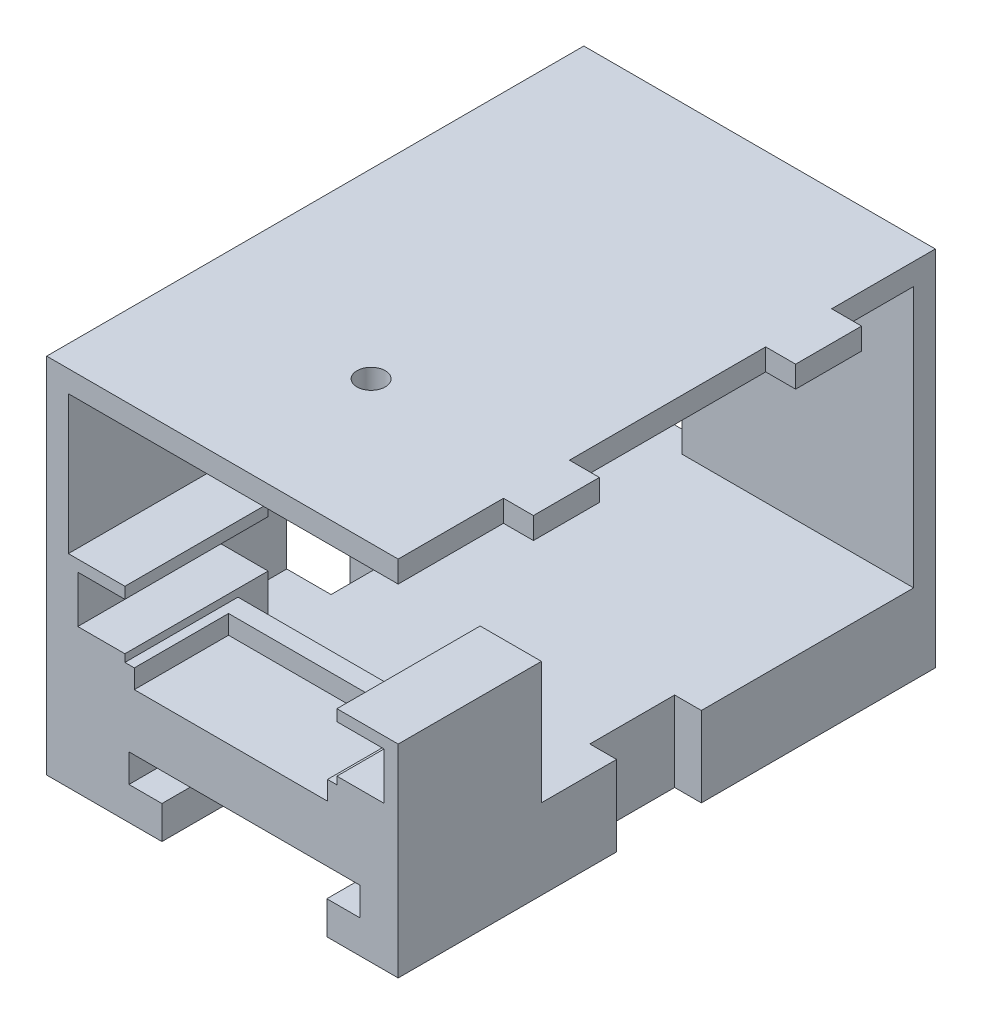
SolidWorks part; units mm, degrees
ref_plane "Front Plane" through (0, 0, 0) normal (0, 0, 1) x (1, 0, 0)
ref_plane "Top Plane" through (0, 0, 0) normal (0, 1, 0) x (1, 0, 0)
ref_plane "Right Plane" through (0, 0, 0) normal (1, 0, 0) x (0, 0, -1)
ref_plane "Plane3" through (0, 0, 53.83) normal (0, 0, 1) x (1, 0, 0)
sketch "Sketch1" plane through (0, 0, 0) normal (1, 0, 0) x (0, 0, -1)
  line L0 (0, 40.694) -> (0, 2.194)
  line L1 (0, 1.7462) -> (0, -1.7462) construction
  line L8 (-53.825, 2.194) -> (-53.825, 40.694)
  line L13 (-53.825, 40.694) -> (0, 40.694)
  line L19 (-53.825, 2.194) -> (0, 2.194)
  dimension "D1" = 0
extrude "main extrude" add sketch "Sketch1" along normal blind 2.3
sketch "Sketch3" plane through (2.3, 0, 0) normal (1, 0, 0) x (0, 0, -1)
  line L4 (-2.3, 38.394) -> (-2.3, 10.694)
  line L8 (-53.825, 38.394) -> (-2.3, 38.394)
  line L13 (-53.825, 40.694) -> (-53.825, 38.394)
  line L14 (-53.825, 40.694) -> (0, 40.694)
  line L15 (0, 40.694) -> (0, 2.194)
  line L16 (0, 2.194) -> (-53.825, 2.194)
  line L19 (-53.825, 10.694) -> (-2.3, 10.694)
  line L20 (-53.825, 40.694) -> (-53.825, 2.194) construction
  line L22 (-53.825, 10.694) -> (-53.825, 2.194)
  dimension "D1" = 2.3
  dimension "D2" = 2.3
extrude "walls" add sketch "Sketch3" along normal blind 35
sketch "Sketch36" plane through (0, 0, 53.825) normal (0, 0, 1) x (1, 0, 0)
  line L0 (37.3, 40.694) -> (0, 40.694) construction
  line L1 (8, 40.694) -> (15, 40.694)
  line L2 (8, 40.694) -> (8, 38.394)
  line L3 (8, 38.394) -> (15, 38.394)
  line L4 (15, 40.694) -> (15, 38.394)
  line L5 (37.3, 38.394) -> (2.3, 38.394) construction
  line L6 (37.3, 38.394) -> (2.3, 38.394) construction
  line L7 (23, 40.694) -> (30, 40.694)
  line L8 (23, 40.694) -> (23, 38.394)
  line L9 (23, 38.394) -> (30, 38.394)
  line L10 (30, 40.694) -> (30, 38.394)
  line L11 (0, 40.694) -> (0, 2.194) construction
  line L12 (0, 32.694) -> (2.3, 32.694)
  line L13 (0, 32.694) -> (0, 25.694)
  line L14 (0, 25.694) -> (2.3, 25.694)
  line L15 (2.3, 32.694) -> (2.3, 25.694)
  line L16 (2.3, 38.394) -> (2.3, 10.694) construction
  line L17 (2.3, 38.394) -> (2.3, 10.694) construction
  line L18 (0, 17.694) -> (2.3, 17.694)
  line L19 (0, 17.694) -> (0, 10.694)
  line L20 (0, 10.694) -> (2.3, 10.694)
  line L21 (2.3, 17.694) -> (2.3, 10.694)
  dimension "D1" = 8
  dimension "D2" = 8
  dimension "D3" = 7
  dimension "D4" = 7
  dimension "D5" = 7
  dimension "D6" = 7
  dimension "D7" = 8
  dimension "D8" = 8
extrude "Puzzle (main walls)" add sketch "Sketch36" along normal blind 3.175
sketch "Sketch25" plane through (0, 0, 2.3) normal (0, 0, 1) x (1, 0, 0)
  line L1 (2.3, 10.694) -> (12.703, 10.694)
  line L2 (2.3, 10.694) -> (2.3, 17.2991)
  line L3 (2.3, 17.2991) -> (12.703, 17.2991)
  line L4 (12.703, 10.694) -> (12.703, 17.2991)
extrude "Wire Hole" cut sketch "Sketch25" against normal through all
sketch "Sketch19" plane through (0, 10.694, 0) normal (0, 1, 0) x (1, 0, 0)
  line L16 (37.3, -41.8) -> (37.3, -53.825)
  line L18 (30.8, -53.825) -> (37.3, -53.825)
  line L27 (37.3, 0) -> (37.3, -53.825) construction
  line L40 (30.8, -53.825) -> (30.8, -41.8)
  line L41 (30.8, -41.8) -> (37.3, -41.8)
  line L47 (2.3, -53.825) -> (8.3, -53.825)
  line L48 (2.3, -53.825) -> (2.3, -41.8)
  line L49 (2.3, -41.8) -> (8.3, -41.8)
  line L50 (8.3, -53.825) -> (8.3, -41.8)
extrude "IR mount" add sketch "Sketch19" along normal blind 7
sketch "Sketch24" plane through (0, 0, 53.83) normal (0, 0, 1) x (1, 0, 0)
  line L0 (37.3, 2.194) -> (0, 2.194) construction
  line L1 (12.23, 2.194) -> (29.73, 2.194)
  line L2 (12.23, 2.194) -> (12.23, 5.694)
  line L4 (29.73, 2.194) -> (29.73, 5.694)
  line L5 (12.23, 5.694) -> (8.73, 5.694)
  line L6 (8.73, 5.694) -> (8.73, 8.694)
  line L9 (33.23, 8.694) -> (33.23, 5.694)
  line L10 (33.23, 5.694) -> (29.73, 5.694)
  line L11 (0, 10.694) -> (0, 2.194) construction
  line L12 (8.73, 8.694) -> (33.23, 8.694)
  dimension "D1" = 8.73
  dimension "D2" = 0
  dimension "D3" = 3.5
  dimension "D4" = 3
  dimension "D5" = 3
  dimension "D6" = 3.5
  dimension "D7" = 3.5
  dimension "D8" = 3.5
  dimension "D9" = 17.5
extrude "Magnet Mount Hole" cut sketch "Sketch24" against normal blind 51.83
sketch "Sketch40" plane through (0, 40.694, 0) normal (0, 1, 0) x (1, 0, 0)
  line L0 (37.3, 0) -> (37.3, -53.825) construction
  line L1 (0, 0) -> (0, -53.825) construction
  circle A0 centre (19.3, -41.8726) radius 1.5
  dimension "D1" = 3
  dimension "D2" = 18
  dimension "D3" = 19.3
extrude "LED Space" cut sketch "Sketch40" against normal blind 3
sketch "Sketch42" plane through (37.3, 0, 0) normal (1, 0, 0) x (0, 0, -1)
  line L0 (0, 40.694) -> (-53.825, 40.694) construction
  line L1 (-45.825, 40.694) -> (-38.825, 40.694)
  line L2 (-45.825, 40.694) -> (-45.825, 38.394)
  line L3 (-45.825, 38.394) -> (-38.825, 38.394)
  line L4 (-38.825, 40.694) -> (-38.825, 38.394)
  line L5 (-53.825, 38.394) -> (-2.3, 38.394) construction
  line L6 (-53.825, 38.394) -> (-2.3, 38.394) construction
  line L7 (-18, 40.694) -> (-11, 40.694)
  line L8 (-18, 40.694) -> (-18, 38.394)
  line L9 (-18, 38.394) -> (-11, 38.394)
  line L10 (-11, 40.694) -> (-11, 38.394)
  line L11 (-53.825, 40.694) -> (-53.825, 38.394) construction
  line L12 (0, 2.194) -> (0, 40.694) construction
  dimension "D1" = 8
  dimension "D2" = 7
  dimension "D3" = 7
  dimension "D4" = 11
extrude "Boss-Extrude15" add sketch "Sketch42" along normal blind 3.175
sketch "Sketch44" plane through (0, 17.694, 0) normal (0, 1, 0) x (1, 0, 0)
  line L1 (2.3, -41.8) -> (8.3, -41.8)
  line L2 (2.3, -41.8) -> (2.3, -53.825)
  line L3 (2.3, -53.825) -> (8.3, -53.825)
  line L4 (8.3, -41.8) -> (8.3, -53.825)
  line L5 (30.8, -41.8) -> (37.3, -41.8)
  line L6 (30.8, -41.8) -> (30.8, -53.825)
  line L7 (30.8, -53.825) -> (37.3, -53.825)
  line L8 (37.3, -41.8) -> (37.3, -53.825)
extrude "Boss-Extrude16" add sketch "Sketch44" along normal blind 6
sketch "Sketch45" plane through (0, 0, 53.825) normal (0, 0, 1) x (1, 0, 0)
  line L0 (30.8, 23.694) -> (30.8, 10.694) construction
  line L1 (30.8, 22.494) -> (35.8, 22.494)
  line L2 (30.8, 22.494) -> (30.8, 17.494)
  line L3 (30.8, 17.494) -> (35.8, 17.494)
  line L4 (35.8, 22.494) -> (35.8, 17.494)
  line L5 (8.3, 23.694) -> (8.3, 10.694) construction
  line L6 (8.3, 22.494) -> (3.3, 22.494)
  line L7 (8.3, 22.494) -> (8.3, 17.494)
  line L8 (8.3, 17.494) -> (3.3, 17.494)
  line L9 (3.3, 22.494) -> (3.3, 17.494)
  line L10 (2.3, 23.694) -> (8.3, 23.694) construction
  line L11 (30.8, 23.694) -> (37.3, 23.694) construction
  dimension "D1" = 1.2
  dimension "D2" = 1.2
  dimension "D3" = 5
  dimension "D4" = 5
  dimension "D5" = 5
  dimension "5" = 5
extrude "IR placement" cut sketch "Sketch45" against normal up to surface (12.025 mm away) up to face at (5.3, 17.194, 41.8)
sketch "Sketch47" plane through (0, 0, 0) normal (0, 0, -1) x (-1, 0, 0)
  circle A0 centre (-21.019, 5.2627) radius 2.5
  dimension "D1" = 5
extrude "Cut-Extrude2" cut sketch "Sketch47" against normal up to surface (2 mm away) up to face at (20.98, 5.569, 2)
sketch "Sketch48" plane through (0, 2.194, 0) normal (0, -1, 0) x (1, 0, 0)
  line L0 (0, 53.825) -> (0, 0) construction
  line L1 (0, 33.825) -> (7, 33.825)
  line L2 (0, 33.825) -> (0, 24.825)
  line L3 (0, 24.825) -> (7, 24.825)
  line L4 (7, 33.825) -> (7, 24.825)
  line L5 (34.4625, 33.825) -> (41.4625, 33.825)
  line L6 (34.4625, 33.825) -> (34.4625, 24.825)
  line L7 (34.4625, 24.825) -> (41.4625, 24.825)
  line L8 (41.4625, 33.825) -> (41.4625, 24.825)
  line L9 (37.3, 53.825) -> (29.73, 53.825) construction
  line L10 (12.23, 53.825) -> (0, 53.825) construction
  dimension "D1" = 20
  dimension "D2" = 20
  dimension "D3" = 9
extrude "Cut-Extrude3" cut sketch "Sketch48" against normal blind 15
sketch "Sketch50" plane through (0, 0, 53.825) normal (0, 0, 1) x (1, 0, 0)
  line L0 (37.3, 38.394) -> (2.3, 38.394)
  line L1 (0, 40.694) -> (37.3, 40.694)
  line L4 (37.3, 40.694) -> (37.3, 38.394)
  line L5 (2.3, 38.394) -> (2.3, 23.694)
  line L6 (2.3, 23.694) -> (8.3, 23.694)
  line L7 (8.3, 23.694) -> (8.3, 22.494)
  line L8 (8.3, 23.694) -> (8.3, 22.494) construction
  line L9 (8.3, 22.494) -> (3.3, 22.494)
  line L10 (3.3, 22.494) -> (3.3, 17.494)
  line L11 (3.3, 17.494) -> (8.3, 17.494)
  line L12 (8.3, 17.494) -> (8.3, 10.694)
  line L13 (8.3, 10.694) -> (30.8, 10.694)
  line L14 (30.8, 10.694) -> (30.8, 17.494)
  line L15 (30.8, 17.494) -> (30.8, 10.694) construction
  line L16 (30.8, 17.494) -> (35.8, 17.494)
  line L17 (35.8, 17.494) -> (35.8, 22.494)
  line L18 (30.8, 23.694) -> (37.3, 23.694)
  line L20 (30.8, 23.694) -> (30.8, 22.494)
  line L21 (30.8, 23.694) -> (30.8, 22.494) construction
  line L23 (29.73, 2.194) -> (29.73, 5.694)
  line L24 (29.73, 5.694) -> (33.23, 5.694)
  line L25 (33.23, 5.694) -> (33.23, 8.694)
  line L26 (33.23, 8.694) -> (8.73, 8.694)
  line L27 (8.73, 8.694) -> (8.73, 5.694)
  line L28 (8.73, 5.694) -> (12.23, 5.694)
  line L29 (12.23, 5.694) -> (12.23, 2.194)
  line L30 (0, 40.694) -> (0, 2.194)
  line L31 (37.3, 23.694) -> (37.3, 2.194)
  line L32 (0, 2.194) -> (12.23, 2.194)
  line L33 (29.73, 2.194) -> (37.3, 2.194)
  line L34 (30.8, 22.494) -> (35.8, 22.494)
extrude "Boss-Extrude17" add sketch "Sketch50" along normal blind 3.175
ref_plane "Plane5" through (37.3, 0, 0) normal (1, 0, 0) x (0, 0, -1)
sketch "Sketch6" [suppressed] plane through (0, 0, 53.83) normal (0, 0, 1) x (1, 0, 0)
  line L2 (0, 40.694) -> (0, 2.194)
  line L6 (0, 40.694) -> (40.48, 40.694)
  line L7 (40.48, 40.694) -> (40.48, 2.194)
  line L8 (0, 2.194) -> (40.48, 2.194)
extrude "front lid" [suppressed] add sketch "Sketch6" along normal blind 3.175 separate body
sketch "Sketch7" [suppressed] plane through (0, 0, 57.005) normal (0, 0, 1) x (1, 0, 0)
  line L0 (0, 2.194) -> (40.48, 2.194) construction
  line L6 (0, -21.175) -> (0, 21.175) construction
  line L10 (19.75, 17.854) -> (27.25, 17.854)
  line L11 (19.75, 17.854) -> (12.25, 17.854)
  line L12 (12.25, 17.854) -> (12.25, 32.854)
  line L13 (12.25, 32.854) -> (27.25, 32.854)
  line L14 (27.25, 17.854) -> (27.25, 32.854)
  circle A0 centre (19.75, 25.354) radius 7.5 construction
  point P12 (19.75, 25.354)
  dimension "D1" = 15
  dimension "D2" = 19.75
  dimension "D4" = 15.66
extrude "nosepoke hole" [suppressed] cut sketch "Sketch7" against normal blind 3.175
sketch "Sketch34" [suppressed] plane through (0, 0, 57.005) normal (0, 0, 1) x (1, 0, 0)
  line L0 (0, 40.694) -> (0, 2.194) construction
  line L1 (0, 32.694) -> (2.3, 32.694)
  line L2 (0, 32.694) -> (0, 25.694)
  line L3 (0, 25.694) -> (2.3, 25.694)
  line L4 (2.3, 32.694) -> (2.3, 25.694)
  line L9 (40.48, 40.694) -> (0, 40.694) construction
  line L10 (8, 40.694) -> (15, 40.694)
  line L11 (8, 40.694) -> (8, 38.394)
  line L12 (8, 38.394) -> (15, 38.394)
  line L13 (15, 40.694) -> (15, 38.394)
  line L14 (23, 40.694) -> (30, 40.694)
  line L15 (23, 40.694) -> (23, 38.394)
  line L16 (23, 38.394) -> (30, 38.394)
  line L17 (30, 40.694) -> (30, 38.394)
  line L23 (40.48, 2.194) -> (40.48, 40.694) construction
  line L24 (0, 17.694) -> (2.3, 17.694)
  line L25 (0, 17.694) -> (0, 10.694)
  line L26 (0, 10.694) -> (2.3, 10.694)
  line L27 (2.3, 17.694) -> (2.3, 10.694)
  line L32 (40.48, 32.694) -> (37.305, 32.694)
  line L33 (40.48, 32.694) -> (40.48, 25.694)
  line L34 (40.48, 25.694) -> (37.305, 25.694)
  line L35 (37.305, 32.694) -> (37.305, 25.694)
  line L37 (40.48, 17.694) -> (37.305, 17.694)
  line L38 (40.48, 17.694) -> (40.48, 10.694)
  line L39 (40.48, 10.694) -> (37.305, 10.694)
  line L40 (37.305, 17.694) -> (37.305, 10.694)
  point P16 (15, 39.544)
  dimension "D1" = 8
  dimension "D2" = 8
  dimension "D3" = 8
  dimension "D4" = 8
  dimension "D5" = 8
  dimension "D6" = 7
  dimension "D7" = 7
  dimension "D8" = 2.3
  dimension "D9" = 8
extrude "Puzzle (Front Lid)" [suppressed] cut sketch "Sketch34" against normal up to surface (3.175 mm away) up to face at (21.019, 7.7627, 0)
sketch "Sketch46" [suppressed] plane through (0, 0, 57.005) normal (0, 0, 1) x (1, 0, 0)
  line L0 (12.23, 2.194) -> (29.73, 2.194)
  line L1 (12.23, 2.194) -> (12.23, 5.694)
  line L2 (29.73, 2.194) -> (29.73, 5.694)
  line L3 (12.23, 5.694) -> (8.73, 5.694)
  line L4 (8.73, 5.694) -> (8.73, 8.694)
  line L5 (33.23, 8.694) -> (33.23, 5.694)
  line L6 (33.23, 5.694) -> (29.73, 5.694)
  line L7 (8.73, 8.694) -> (33.23, 8.694)
  line L8 (0, 10.694) -> (0, 2.194) construction
  line L10 (0, 2.194) -> (40.48, 2.194) construction
  dimension "D1" = 8.73
  dimension "D3" = 3
  dimension "D4" = 3.5
  dimension "D5" = 0
  dimension "D6" = 3.5
  dimension "D7" = 3
  dimension "D8" = 3.5
  dimension "D9" = 3.5
  dimension "D10" = 17.5
extrude "magnet mount front lid" [suppressed] cut sketch "Sketch46" against normal up to surface (3.175 mm away) up to face at (19.8657, 17.2583, 57)
sketch "Lever Space in Operant (reference)" [suppressed] plane through (0, 0, 57.005) normal (0, 0, 1) x (1, 0, 0)
  line L1 (2.88, 34.514) -> (34.4305, 34.514) construction
  line L2 (2.88, 34.514) -> (2.88, 17.854) construction
  line L3 (2.88, 17.854) -> (34.4305, 17.854) construction
  line L4 (34.4305, 34.514) -> (34.4305, 17.854) construction
  line L7 (0, -21.175) -> (0, 21.175) construction
  line L8 (2.3, 10.694) -> (2.3, 38.394) construction
  line L9 (12.25, 32.854) -> (27.25, 32.854) construction
  line L10 (12.25, 32.854) -> (12.25, 17.854) construction
  line L11 (12.25, 17.854) -> (27.25, 17.854) construction
  line L12 (27.25, 32.854) -> (27.25, 17.854) construction
  line L14 (0, 2.194) -> (40.48, 2.194) construction
  dimension "D1" = 15.66
  dimension "D2" = 2.88
  dimension "D3" = 31.5505
  dimension "D4" = 16.66
ref_plane "contact face with wall" [suppressed] through (0, 0, 57.005) normal (0, 0, 1) x (1, 0, 0)
sketch "Acrylic Guard (reference)" [suppressed] plane through (0, 0, 53.83) normal (0, 0, -1) x (-1, 0, 0)
  line L0 (7.75, 32.854) -> (50007.75, 32.854) construction
  line L1 (-27.25, 32.854) -> (-27.25, 17.854)
  line L2 (-27.25, 17.854) -> (-12.25, 17.854)
  line L3 (-12.25, 17.854) -> (-12.25, 32.854)
  line L4 (-12.25, 32.854) -> (-9.25, 32.854)
  line L5 (-9.25, 32.854) -> (-9.25, 14.854)
  line L6 (-9.25, 14.854) -> (-30.25, 14.854)
  line L7 (-30.25, 14.854) -> (-30.25, 32.854)
  line L8 (-30.25, 32.854) -> (-27.25, 32.854)
  dimension "D1" = 3
sketch "Sketch20" [suppressed] plane through (37.3, 0, 0) normal (1, 0, 0) x (0, 0, -1)
  line L1 (-53.825, 40.694) -> (0, 40.694)
  line L2 (-53.825, 40.694) -> (-53.825, 2.194)
  line L3 (-53.825, 2.194) -> (0, 2.194)
  line L4 (0, 40.694) -> (0, 2.194)
extrude "Side main" [suppressed] add sketch "Sketch20" along normal blind 3.175 separate body
sketch "Sketch37" [suppressed] plane through (0, 0, 53.825) normal (0, 0, 1) x (1, 0, 0)
  line L0 (37.3, 40.694) -> (37.3, 2.194) construction
  line L1 (37.3, 32.694) -> (40.475, 32.694)
  line L2 (37.3, 32.694) -> (37.3, 25.694)
  line L3 (37.3, 25.694) -> (40.475, 25.694)
  line L4 (40.475, 32.694) -> (40.475, 25.694)
  line L5 (40.475, 40.694) -> (40.475, 2.194) construction
  line L6 (40.475, 40.694) -> (37.3, 40.694) construction
  line L7 (37.3, 17.694) -> (40.475, 17.694)
  line L8 (37.3, 17.694) -> (37.3, 10.694)
  line L9 (37.3, 10.694) -> (40.475, 10.694)
  line L10 (40.475, 17.694) -> (40.475, 10.694)
  dimension "D1" = 8
  dimension "D2" = 7
  dimension "D3" = 8
  dimension "D4" = 7
extrude "Puzzle (side part)" [suppressed] add sketch "Sketch37" along normal blind 3.175
sketch "Sketch41" [suppressed] plane through (40.475, 0, 0) normal (1, 0, 0) x (0, 0, -1)
  line L0 (0, 40.694) -> (-53.825, 40.694) construction
  line L1 (-45.825, 40.694) -> (-38.825, 40.694)
  line L2 (-45.825, 40.694) -> (-45.825, 38.394)
  line L3 (-45.825, 38.394) -> (-38.825, 38.394)
  line L4 (-38.825, 40.694) -> (-38.825, 38.394)
  line L5 (-53.825, 40.694) -> (-53.825, 2.194) construction
  line L6 (-18, 40.694) -> (-11, 40.694)
  line L7 (-18, 40.694) -> (-18, 38.394)
  line L8 (-18, 38.394) -> (-11, 38.394)
  line L9 (-11, 40.694) -> (-11, 38.394)
  line L10 (0, 2.194) -> (0, 40.694) construction
  dimension "D1" = 8
  dimension "D2" = 11
  dimension "D3" = 7
extrude "Cut-Extrude1" [suppressed] cut sketch "Sketch41" against normal up to surface (3.175 mm away) up to face at (37.3, 12.194, 44.2083)
sketch "Sketch49" [suppressed] plane through (0, 2.194, 0) normal (0, -1, 0) x (1, 0, 0)
  line L0 (40.475, 53.825) -> (40.475, 0) construction
  line L1 (40.475, 33.825) -> (33.475, 33.825)
  line L2 (40.475, 33.825) -> (40.475, 24.825)
  line L3 (40.475, 24.825) -> (33.475, 24.825)
  line L4 (33.475, 33.825) -> (33.475, 24.825)
  line L5 (40.475, 53.825) -> (37.3, 53.825) construction
  dimension "D1" = 20
extrude "Cut-Extrude4" [suppressed] cut sketch "Sketch49" against normal blind 15
sketch "Sketch51" plane through (0, 10.694, 0) normal (0, 1, 0) x (1, 0, 0)
  line L0 (8.3, -57) -> (8.3, -41.8) construction
  line L1 (30.8, -57) -> (8.3, -57)
  line L2 (30.8, -57) -> (30.8, -47)
  line L3 (30.8, -47) -> (8.3, -47)
  line L4 (8.3, -57) -> (8.3, -47)
extrude "Boss-Extrude18" add sketch "Sketch51" along normal blind 4
sketch "Sketch52" plane through (0, 10.694, 0) normal (0, 1, 0) x (1, 0, 0)
  line L0 (30.8, -41.8) -> (30.8, -47) construction
  line L1 (9.3, -47) -> (29.8, -47)
  line L2 (8.3, -47) -> (8.3, -45)
  line L3 (8.3, -45) -> (30.8, -45)
  line L4 (30.8, -47) -> (30.8, -45)
  line L5 (37.3, -57) -> (0, -57) construction
  line L7 (8.3, -47) -> (8.3, -57)
  line L8 (8.3, -57) -> (9.3, -57)
  line L9 (9.3, -47) -> (9.3, -57)
  line L12 (30.8, -47) -> (30.8, -57)
  line L13 (30.8, -57) -> (29.8, -57)
  line L14 (29.8, -47) -> (29.8, -57)
extrude "Boss-Extrude19" add sketch "Sketch52" along normal blind 6
sketch "Sketch53" [suppressed] plane through (0, 0, 53.825) normal (0, 0, 1) x (1, 0, 0)
  line L1 (37.3, 40.694) -> (40.475, 40.694)
  line L2 (37.3, 40.694) -> (37.3, 2.194)
  line L3 (37.3, 2.194) -> (40.475, 2.194)
  line L4 (40.475, 40.694) -> (40.475, 2.194)
extrude "Boss-Extrude20" [suppressed] add sketch "Sketch53" along normal blind 3.175
